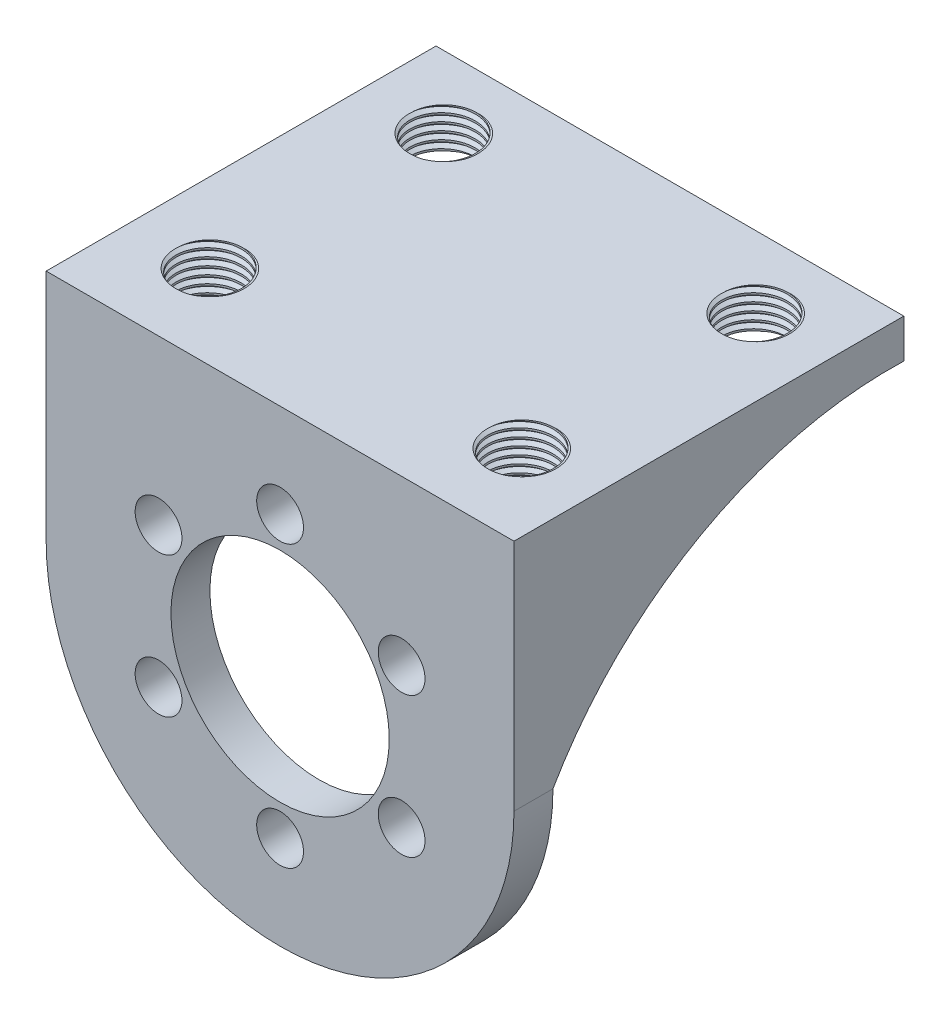
SolidWorks part; units mm, degrees
ref_plane "Спереди" through (0, 0, 0) normal (0, 0, 1) x (1, 0, 0)
ref_plane "Сверху" through (0, 0, 0) normal (0, 1, 0) x (1, 0, 0)
ref_plane "Справа" through (0, 0, 0) normal (1, 0, 0) x (0, 0, -1)
sketch "Эскиз1" plane through (0, 0, 0) normal (0, 0, 1) x (1, 0, 0)
  circle A0 centre (0, 0) radius 7
  circle A1 centre (0, 0) radius 15
  circle A2 centre (0, 0) radius 9 construction
  circle A3 centre (0, 9) radius 1.5
  circle A4 centre (7.7942, 4.5) radius 1.5
  circle A5 centre (7.7942, -4.5) radius 1.5
  circle A6 centre (0, -9) radius 1.5
  circle A7 centre (-7.7942, -4.5) radius 1.5
  circle A8 centre (-7.7942, 4.5) radius 1.5
  point P19 (0, 0)
  dimension "D1" = 14
  dimension "D2" = 30
  dimension "D3" = 18
  dimension "D4" = 3
  dimension "D6" = 9.4248
  dimension "D5" = 6
extrude "Бобышка-Вытянуть1" add sketch "Эскиз1" along normal blind 2.5
sketch "Эскиз4" plane through (0, 0, 0) normal (0, 0, -1) x (-1, 0, 0)
  line L0 (12.5, 0) -> (15, 0)
  line L1 (-15, 15) -> (15, 15)
  line L2 (-15, 15) -> (-15, 0)
  line L3 (-15, 0) -> (-12.5, 0)
  line L4 (15, 15) -> (15, 0)
  line L5 (-15, 15) -> (15, 0) construction
  line L6 (-15, 0) -> (15, 15) construction
  circle A0 centre (0, 0) radius 15 construction
  arc A1 (-12.5, 0) -> (12.5, 0) centre (0, 0) cw
  point P4 (0, 7.5)
  dimension "D4" = 12.5
  dimension "D1" = 15
  dimension "D2" = 30
  dimension "D3" = 15
extrude "Бобышка-Вытянуть4" add sketch "Эскиз4" along normal blind 25 from surface starting at face at (-6.2942, -4.5, 2.5)
sketch "Эскиз5" plane through (15, 0, 0) normal (1, 0, 0) x (0, 0, -1)
  line L0 (22.5, 0) -> (22.5, 15) construction
  line L1 (0, 0) -> (22.5, 0)
  line L2 (22.5, 0) -> (0, 0) construction
  line L3 (22.5, 0) -> (22.5, 12.5)
  arc A0 (22.5, 12.5) -> (0, 0) centre (21.6588, -12.4858) ccw
  dimension "D2" = 25
  dimension "D1" = 12.5
extrude "Вырез-Вытянуть1" cut sketch "Эскиз5" against normal through all both and the other way through all
hole_wizard "Сверление под метчик M51" positions "Эскиз7" profile "Эскиз8" hole size "M5" standard "ISO" end condition through all
sketch "Эскиз7" plane through (0, 15, 0) normal (0, 1, 0) x (1, 0, 0)
  point P0 (-10, 3)
  dimension "D1" = 10
  dimension "D2" = 3
sketch "Эскиз8" plane through (-10, 15, -3) normal (1, 0, 0) x (0, 0, 1)
  line L0 (0, 0) -> (0, 30)
  line L1 (0, 30) -> (2.1, 30)
  line L2 (2.1, 30) -> (2.1, 0)
  line L5 (2.1, 0) -> (0, 0)
  line L11 (0, -6.35) -> (0, 107.95) construction
  dimension "Диаметр сквозного отверстия" = 4.2
  dimension "Глубина сквозного отверстия" = 30
thread "Резьба1" pitch 0.5 method cut profile "Профиль резьбы1" start angle 0, offset 1, length 20, pitch 0.5, diameter 4.2
ref_plane "Плоскость1" through (-12.1, 16, -3) normal (0, 0, 1) x (-1, 0, 0)
sketch "Профиль резьбы1" plane through (-12.1, 16, -3) normal (0, 0, 1) x (-1, 0, 0)
  line L0 (0, 0) -> (0, 0.5) construction
  line L1 (0, 0) -> (0.2706, 0.1562)
  line L2 (0.2706, 0.1562) -> (0.2706, 0.2187)
  line L3 (0.2706, 0.2187) -> (0, 0.375)
  line L4 (0.2706, 0.1875) -> (0, 0.1875) construction
  line L11 (0, 0) -> (0, 0.375)
  point P2 (0, 0)
  dimension "Pitch" = 0.5
  dimension "Profile_Angle" = 60
  dimension "Profile_Land" = 0.0625
  dimension "Profile_Height" = 0.2706
pattern_linear "Линейный массив1" count 2 spacing 20 along (1, 0, 0) count 2 spacing 15 along (0, 0, -1) of "Сверление под метчик M51", "Резьба1"
